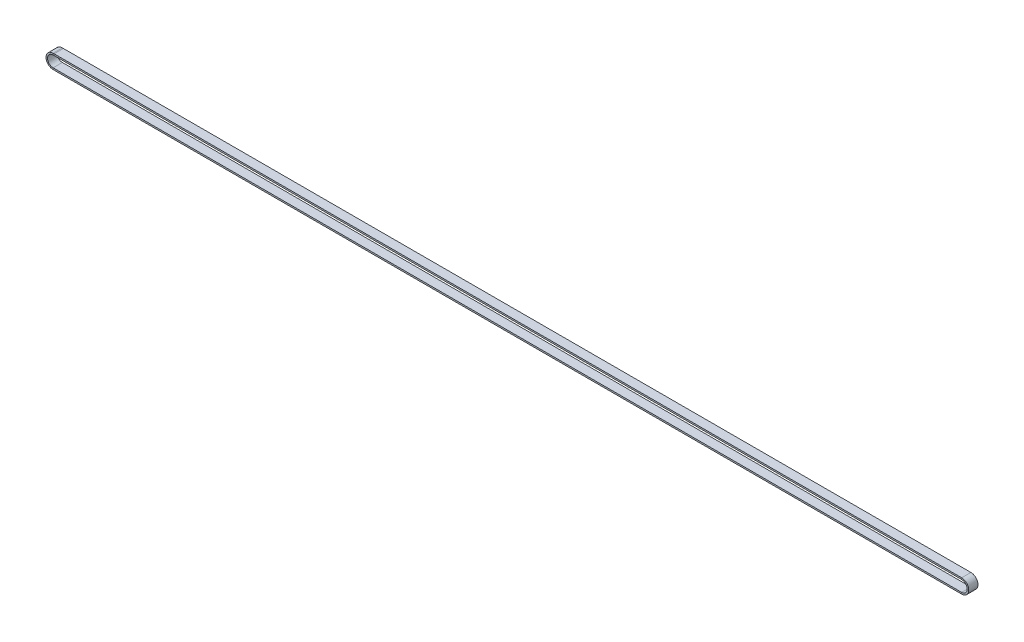
SolidWorks part; units mm, degrees
ref_plane "Front Plane" through (0, 0, 0) normal (0, 0, 1) x (1, 0, 0)
ref_plane "Top Plane" through (0, 0, 0) normal (0, 1, 0) x (1, 0, 0)
ref_plane "Right Plane" through (0, 0, 0) normal (1, 0, 0) x (0, 0, -1)
sketch "Sketch2" plane through (0, 0, 0) normal (0, 0, 1) x (1, 0, 0)
  line L0 (0, 0) -> (1, 0) construction
  line L1 (0, 0) -> (0, 1) construction
  line L2 (-1, -32.1158) -> (883.5206, -32.1158)
  line L3 (883.5206, -45.9158) -> (-1, -45.9158)
  arc A0 (-1, -45.9158) -> (-1, -32.1158) centre (-1, -39.0158) cw
  arc A1 (883.5206, -32.1158) -> (883.5206, -45.9158) centre (883.5206, -39.0158) cw
sketch "Sketch3" plane through (0, 0, 0) normal (1, 0, 0) x (0, 0, -1)
  line L1 (0, -33.6158) -> (-9, -33.6158)
  line L2 (0, -33.6158) -> (0, -32.1158)
  line L3 (0, -32.1158) -> (-9, -32.1158)
  line L4 (-9, -33.6158) -> (-9, -32.1158)
  dimension "D1" = 9
  dimension "D2" = 1.5
sweep "Sweep1" add profiles "Sketch3" path "Sketch2"
